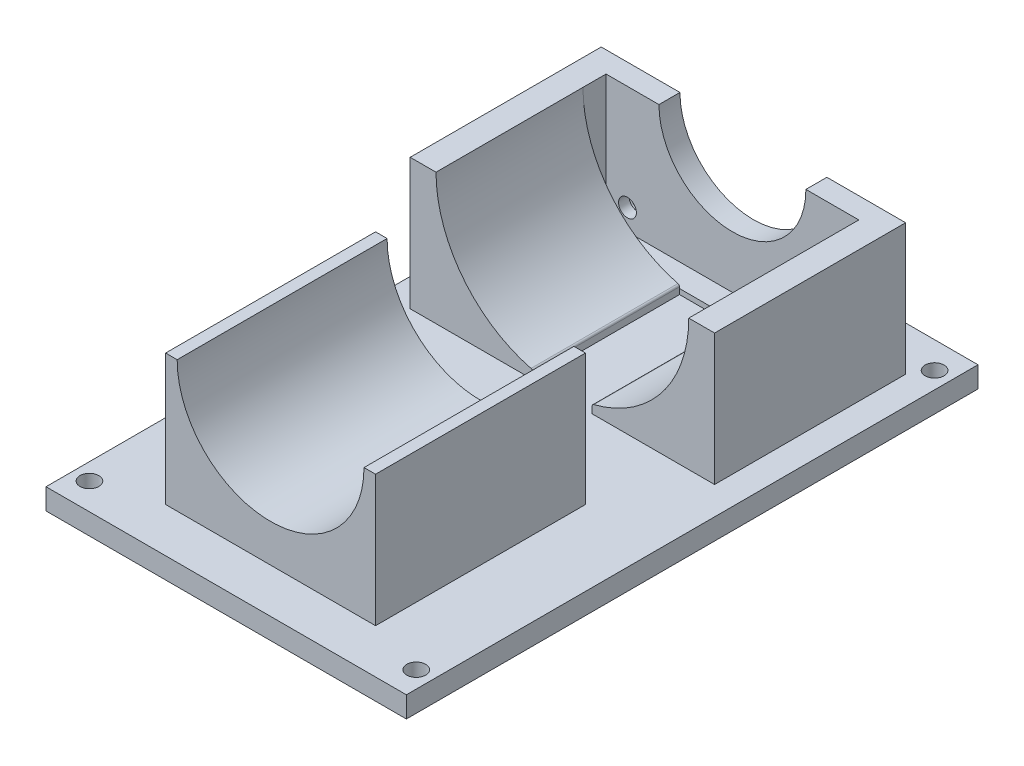
SolidWorks part; units mm, degrees
ref_plane "Front Plane" through (0, 0, 0) normal (0, 0, 1) x (1, 0, 0)
ref_plane "Top Plane" through (0, 0, 0) normal (0, 1, 0) x (1, 0, 0)
ref_plane "Right Plane" through (0, 0, 0) normal (1, 0, 0) x (0, 0, -1)
sketch "Sketch1" plane through (0, 0, 0) normal (0, 0, 1) x (1, 0, 0)
  line L0 (0, 72.5) -> (72.5, 0) construction
  line L1 (0, 0) -> (72.5, 0)
  line L2 (0, 0) -> (0, 72.5)
  line L3 (0, 72.5) -> (72.5, 72.5)
  line L4 (72.5, 0) -> (72.5, 72.5)
  line L6 (0, 0) -> (72.5, 72.5) construction
  circle A4 centre (36.25, 36.25) radius 17.5
  circle A5 centre (11.25, 61.25) radius 2.125
  circle A6 centre (61.25, 61.25) radius 2.125
  circle A7 centre (61.25, 11.25) radius 2.125
  circle A8 centre (11.25, 11.25) radius 2.125
  point P5 (11.25, 11.25)
  point P8 (61.25, 11.25)
  point P15 (36.25, 72.5)
  point P16 (0, 36.25)
  point P17 (61.25, 61.25)
  point P20 (11.25, 61.25)
  dimension "D1" = 50
  dimension "D8" = 35
  dimension "D4" = 4.25
  dimension "D2" = 50
  dimension "D3" = 72.5
extrude "Boss-Extrude1" add sketch "Sketch1" along normal blind 5
ref_plane "Plane1" through (0, 0, 65) normal (0, 0, 1) x (1, 0, 0)
sketch "Sketch18" plane through (0, 0, 0) normal (0, 0, 1) x (1, 0, 0)
  circle A0 centre (61.25, 61.25) radius 5
  circle A1 centre (11.25, 61.25) radius 5
  circle A2 centre (61.25, 11.25) radius 5
  circle A3 centre (11.25, 11.25) radius 5
  dimension "D1" = 10
sketch "Sketch5" plane through (0, 0, 65) normal (0, 0, 1) x (1, 0, 0)
  line L0 (0, 0) -> (72.5, 0)
  line L1 (11.25, 36.25) -> (14, 36.25)
  line L2 (11.25, 36.25) -> (11.25, 5)
  line L4 (0, 0) -> (0, 5)
  line L5 (0, 72.5) -> (0, 0) construction
  line L6 (0, 5) -> (11.25, 5)
  line L7 (36.25, 72.5) -> (36.25, 0) construction
  line L8 (72.5, 72.5) -> (0, 72.5) construction
  line L9 (72.5, 5) -> (61.25, 5)
  line L11 (72.5, 0) -> (72.5, 5)
  line L12 (61.25, 36.25) -> (58.5, 36.25)
  line L13 (61.25, 36.25) -> (61.25, 5)
  arc A2 (14, 36.25) -> (58.5, 36.25) centre (36.25, 36.25) ccw
  dimension "D4" = 22.25
  dimension "D2" = 5
  dimension "D3" = 25
extrude "Boss-Extrude2" add sketch "Sketch5" along normal blind 50 separate body
extrude "Cut-Extrude1" cut sketch "Sketch18" along direction (0, 0, -1) on the side of the normal blind 2.5
ref_plane "Plane4" through (0, 5, 0) normal (0, 1, 0) x (1, 0, 0)
sketch "Sketch7" plane through (0, 0, 5) normal (0, 0, 1) x (1, 0, 0)
  line L0 (0, 0) -> (72.5, 0)
  line L5 (72.5, 0) -> (72.5, 36.25)
  line L6 (72.5, 0) -> (72.5, 72.5) construction
  line L7 (72.5, 36.25) -> (66.35, 36.25)
  line L8 (66.35, 36.25) -> (66.35, 5)
  line L9 (72.5, 5) -> (61.25, 5) construction
  line L10 (66.35, 5) -> (6.15, 5)
  line L12 (6.15, 5) -> (6.15, 36.25)
  line L13 (6.15, 36.25) -> (0, 36.25)
  line L14 (0, 72.5) -> (0, 0) construction
  line L15 (0, 36.25) -> (0, 0)
  point P4 (0, 0)
  dimension "D1" = 60.2
extrude "Boss-Extrude3" add sketch "Sketch7" along normal blind 5.5
sketch "Sketch8" plane through (0, 0, 65) normal (0, 0, 1) x (1, 0, 0)
  line L1 (0, 0) -> (72.5, 0)
  line L2 (0, 0) -> (0, 5)
  line L3 (0, 5) -> (72.5, 5)
  line L4 (72.5, 0) -> (72.5, 5)
extrude "Boss-Extrude4" add sketch "Sketch8" against normal up to surface (54.5 mm away) up to face at (36.25, 19.375, 10.5)
ref_plane "Plane3" through (0, 0, 10.5) normal (0, 0, 1) x (1, 0, 0)
sketch "Sketch11" plane through (0, 0, 10.5) normal (0, 0, 1) x (1, 0, 0)
  line L0 (0, 5) -> (29.1474, 5)
  line L1 (66.35, 5) -> (6.15, 5) construction
  line L2 (72.5, 5) -> (43.3526, 5)
  line L3 (0, 72.5) -> (72.5, 0) construction
  line L4 (29.1474, 7) -> (29.1474, 5)
  line L5 (43.3526, 5) -> (43.3526, 7)
  line L12 (6.15, 36.25) -> (0, 36.25)
  line L13 (0, 36.25) -> (0, 5)
  line L14 (66.35, 36.25) -> (72.5, 36.25)
  line L15 (72.5, 36.25) -> (72.5, 5)
  arc A0 (6.15, 36.25) -> (29.1474, 7) centre (36.25, 36.25) ccw
  arc A1 (66.35, 36.25) -> (43.3526, 7) centre (36.25, 36.25) cw
  dimension "D1" = 2
extrude "Boss-Extrude5" add sketch "Sketch11" along normal blind 35
sketch "Sketch17" plane through (0, 5, 0) normal (0, 1, 0) x (1, 0, 0)
  line L0 (6.15, -5) -> (6.15, -10.5)
  line L1 (-37.8926, -10.5) -> (37.8926, -10.5) construction
  line L2 (6.15, -45.5) -> (6.15, -10.5) construction
  line L3 (6.15, -10.5) -> (66.4659, -10.5)
  line L4 (66.4659, -10.5) -> (66.35, -5)
  line L5 (66.35, -5) -> (6.15, -5)
extrude "Boss-Extrude7" add sketch "Sketch17" along normal blind 1.25
sketch "Sketch12" plane through (0, 0, 0) normal (0, 1, 0) x (1, 0, 0)
  line L0 (-6.6663, -125.5741) -> (79.1663, 10.5741) construction
  line L1 (-6.6663, 10.5741) -> (79.1663, -125.5741) construction
  line L2 (-6.6663, -125.5741) -> (79.1663, -125.5741)
  line L3 (-6.6663, -125.5741) -> (-6.6663, 10.5741)
  line L4 (-6.6663, 10.5741) -> (79.1663, 10.5741)
  line L5 (79.1663, -125.5741) -> (79.1663, 10.5741)
  line L6 (-3.3331, 10.5741) -> (-3.3331, -125.5741) construction
  line L8 (14.3178, 10.5741) -> (14.3178, 0) construction
  line L9 (72.5, 0) -> (0, 0) construction
  line L11 (75.8331, 10.5741) -> (75.8331, -125.5741) construction
  line L12 (72.5, -57.5) -> (79.1663, -57.5) construction
  line L14 (72.5, -45.5) -> (72.5, -5) construction
  line L15 (-6.6663, -3.6553) -> (0, -3.6553) construction
  line L16 (0, -5) -> (0, 0) construction
  circle A0 centre (-2.6665, 4.2296) radius 2.25
  circle A1 centre (75.1665, 4.2296) radius 2.25
  circle A2 centre (75.1665, -119.2296) radius 2.25
  circle A3 centre (-2.6665, -119.2296) radius 2.25
  point P2 (0, 0)
  point P3 (72.9389, 4.0451)
  point P21 (75.8331, -57.5)
  point P26 (-3.3331, -3.6553)
  point P34 (-2.9389, 4.0451)
  point P37 (-2.9389, -100.3951)
  point P38 (72.9389, -100.3951)
  dimension "D6" = 4.5
  dimension "D1" = 12.5
  dimension "D2" = 12.5
  dimension "D7" = 5
  dimension "D8" = 5
  dimension "D9" = 5
  dimension "D10" = 5
extrude "Boss-Extrude6" add sketch "Sketch12" along normal up to surface (5 mm away) up to face at (36.25, 5, 66.0833)
fillet "Fillet10" radius 0.5 2 edges at (43.3526, 7, 28) (29.1474, 7, 28)
ref_plane "Plane8" through (0, 0, 45.5) normal (0, 0, 1) x (1, 0, 0)
sketch "Sketch26" plane through (0, 0, 0) normal (0, 0, 1) x (1, 0, 0)
  line L1 (0, 72.5) -> (72.5, 72.5)
  line L2 (0, 72.5) -> (0, 36.25)
  line L3 (0, 36.25) -> (72.5, 36.25)
  line L4 (72.5, 72.5) -> (72.5, 36.25)
  dimension "D1" = 36.25
extrude "Cut-Extrude3" cut sketch "Sketch26" along normal through all
